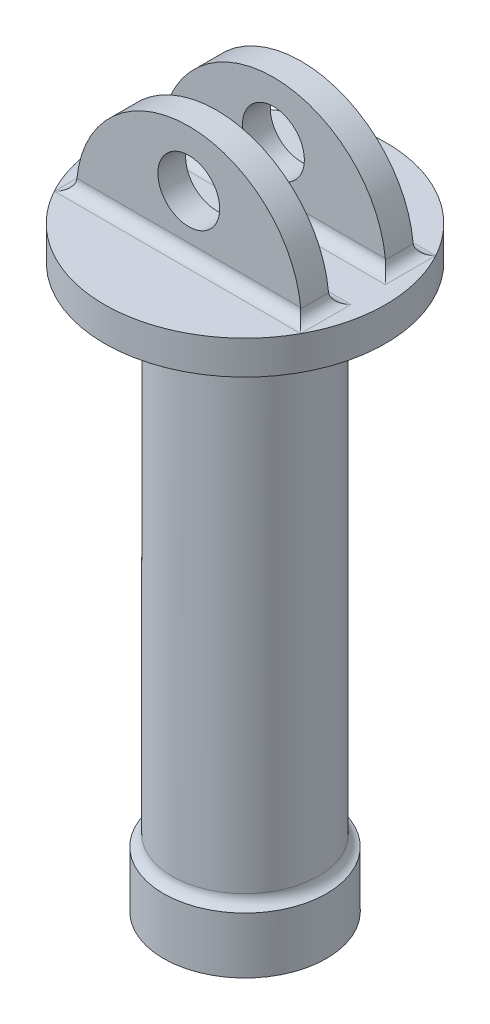
SolidWorks part; units mm, degrees
ref_plane "Front Plane" through (0, 0, 0) normal (0, 0, 1) x (1, 0, 0)
ref_plane "Top Plane" through (0, 0, 0) normal (0, 1, 0) x (1, 0, 0)
ref_plane "Right Plane" through (0, 0, 0) normal (1, 0, 0) x (0, 0, -1)
sketch "Sketch2" plane through (0, 0, 0) normal (0, 1, 0) x (1, 0, 0)
  circle A0 centre (0, 0) radius 13
  circle A1 centre (0, 0) radius 10
  circle A2 centre (0, 0) radius 14.5
extrude "Boss-Extrude3" add sketch "Sketch2" along normal blind 100 separate body contours A0 A1 region at (-12.6323, 0, 0)
extrude "Boss-Extrude5" add sketch "Sketch2<3>" along normal blind 10 contours A2 A0 region at (-14.0899, 0, 0)
sketch "Sketch2<3>" plane through (0, 0, 0) normal (0, 1, 0) x (1, 0, 0) same geometry as "Sketch2"
sketch "Sketch8" plane through (0, 100, 0) normal (0, 1, 0) x (1, 0, 0)
  circle A1 centre (0, 0) radius 25
extrude "Boss-Extrude7" add sketch "Sketch8" along normal blind 6
sketch "Sketch11" plane through (0, 0, 0) normal (0, 0, 1) x (1, 0, 0)
  line L0 (20, 106) -> (-20, 106)
  circle A0 centre (0, 116) radius 5.5
  arc A1 (20, 106) -> (-20, 106) centre (0, 106) ccw
extrude "Boss-Extrude12" add sketch "Sketch11" along normal mid plane 20
sketch "Sketch14" plane through (0, 106, 0) normal (0, 1, 0) x (1, 0, 0)
  line L1 (23.9706, -5.0609) -> (-23.9706, -5.0609)
  line L2 (23.9706, -5.0609) -> (23.9706, 5.0609)
  line L3 (23.9706, 5.0609) -> (-23.9706, 5.0609)
  line L4 (-23.9706, -5.0609) -> (-23.9706, 5.0609)
  line L5 (23.9706, -5.0609) -> (-23.9706, 5.0609) construction
  line L6 (23.9706, 5.0609) -> (-23.9706, -5.0609) construction
  point P0 (0, 0)
extrude "Cut-Extrude2" cut sketch "Sketch14" along normal through all
sketch3d "3DSketch4"
  line L0 (0, 116, -5.0609) -> (0, 116, 5.0609)
fillet "Fillet1" radius 2 10 edges at (-20, 106, 7.5304) (-20, 106, -7.5304) (0, 106, -10) (0, 106, 5.0609) (0, 106, -5.0609) (20, 106, -7.5304) (20, 106, 7.5304) (0, 106, 10) (0, 100, 13) (0, 10, 13)
